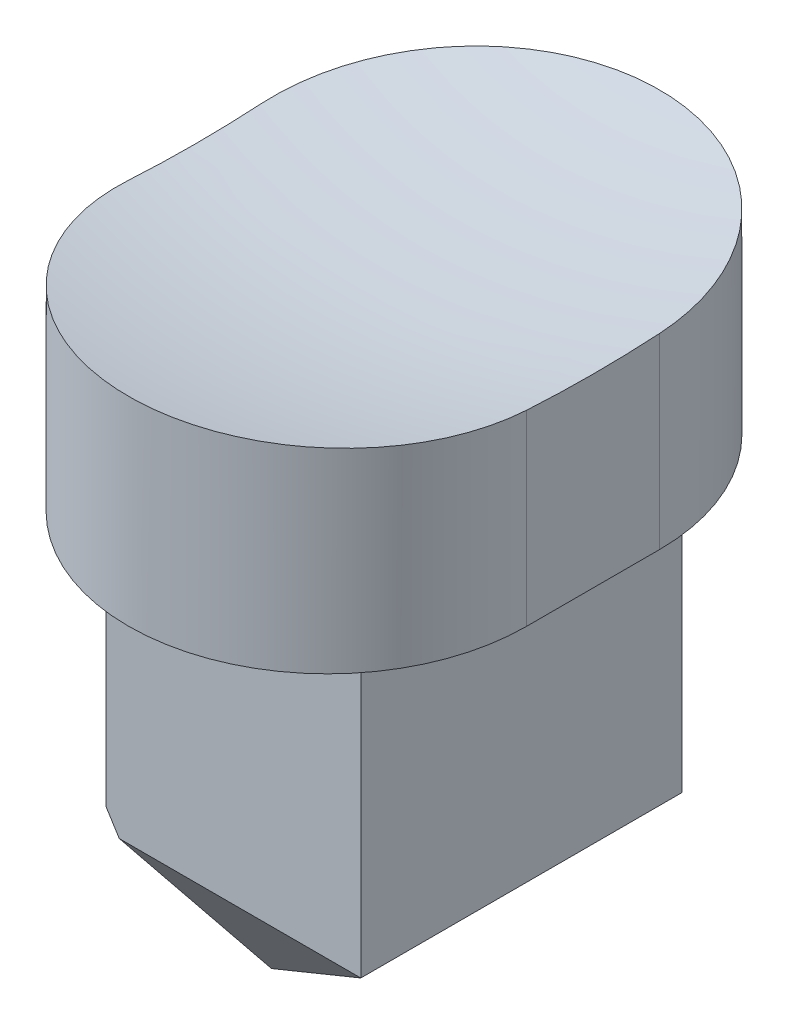
SolidWorks part; units mm, degrees
ref_plane "Front Plane" through (0, 0, 0) normal (0, 0, 1) x (1, 0, 0)
ref_plane "Top Plane" through (0, 0, 0) normal (0, 1, 0) x (1, 0, 0)
ref_plane "Right Plane" through (0, 0, 0) normal (1, 0, 0) x (0, 0, -1)
sketch "Sketch1" plane through (0, 0, 0) normal (0, 1, 0) x (1, 0, 0)
  line L1 (-9.6, 12.1) -> (9.6, 12.1)
  line L2 (-9.6, 12.1) -> (-9.6, -12.1)
  line L3 (-9.6, -12.1) -> (9.6, -12.1)
  line L4 (9.6, 12.1) -> (9.6, -12.1)
  line L5 (-9.6, 12.1) -> (9.6, -12.1) construction
  line L6 (-9.6, -12.1) -> (9.6, 12.1) construction
  point P0 (0, 0)
  dimension "D1" = 19.2
  dimension "D2" = 24.2
extrude "Boss-Extrude1" add sketch "Sketch1" along normal blind 22.1
sketch "Sketch2" plane through (0, 22.1, 0) normal (0, 1, 0) x (1, 0, 0)
  line L0 (0, 5) -> (0, -5) construction
  line L1 (15, 5) -> (15, -5)
  line L2 (-15, 5) -> (-15, -5)
  line L3 (0, 20) -> (0, -20) construction
  line L4 (-9.6, 0) -> (9.6, 0) construction
  line L5 (-9.6, 12.1) -> (-9.6, -12.1) construction
  line L6 (9.6, -12.1) -> (9.6, 12.1) construction
  arc A0 (15, 5) -> (-15, 5) centre (0, 5) ccw
  arc A1 (-15, -5) -> (15, -5) centre (0, -5) ccw
  point P3 (0, 0)
  dimension "D1" = 30
  dimension "D2" = 40
extrude "Boss-Extrude2" add sketch "Sketch2" along normal blind 15
sketch "Sketch4" plane through (-9.6, 0, 0) normal (-1, 0, 0) x (0, 0, 1)
  line L0 (0, 0) -> (0, -15) construction
  line L1 (-12.1, 0) -> (0, -15)
  line L2 (0, -15) -> (12.1, 0)
  line L3 (12.1, 0) -> (-12.1, 0)
  dimension "D1" = 15
extrude "Boss-Extrude3" add sketch "Sketch4" against normal blind 5
sketch "Sketch6" plane through (0, 0, 0) normal (0, 0, 1) x (1, 0, 0)
  line L0 (-4.6, -5) -> (9.6, 0)
  line L1 (-4.6, -15) -> (-4.6, 0) construction
  line L3 (-4.6, -5) -> (-4.6, 0)
  line L4 (-4.6, 0) -> (9.6, 0)
  dimension "D1" = 10
extrude "Boss-Extrude4" add sketch "Sketch6" along normal mid plane 3
fillet "Fillet1" radius 3 2 edges at (-4.6, 0, -6.8) (-4.6, 0, 6.8)
sketch "Sketch8" plane through (0, 0, 0) normal (1, 0, 0) x (0, 0, -1)
  line L0 (-85.2784, 120) -> (85.2784, 120) construction
  line L1 (-85.2784, 120) -> (85.2784, 120)
  line L2 (0, 120) -> (0, 34.7216) construction
  arc A0 (-85.2784, 120) -> (85.2784, 120) centre (0, 120) ccw
  dimension "D1" = 120
revolve "Cut-Revolve3" cut sketch "Sketch8" angle 360 about L1
sketch "Sketch9" plane through (0, 22.1, 0) normal (0, -1, 0) x (1, 0, 0)
  line L4 (9.6, -12.1) -> (-9.6, -12.1) construction
  line L5 (-9.6, -12.1) -> (-9.6, 12.1) construction
  line L6 (-9.6, 12.1) -> (9.6, 12.1) construction
  line L7 (9.6, 12.1) -> (9.6, -12.1) construction
  line L8 (9.6, -12.1) -> (-9.6, -12.1)
  line L9 (-9.6, -12.1) -> (-9.6, 12.1)
  line L10 (-9.6, 12.1) -> (9.6, 12.1)
  line L11 (9.6, 12.1) -> (9.6, -12.1)
extrude "Cut-Extrude-Thin1" cut sketch "Sketch9" against normal blind 10 thin thin type one direction wall 0.3
sketch "Sketch10" plane through (-9.6, 0, 0) normal (-1, 0, 0) x (0, 0, 1)
  line L0 (-12.4, 32.1) -> (12.4, 32.1) construction
  line L1 (-12.4, 32.1) -> (12.4, 32.1)
  line L2 (-12.4, 32.1) -> (-12.4, 32.4)
  line L3 (-12.4, 32.4) -> (12.4, 32.4)
  line L4 (12.4, 32.1) -> (12.4, 32.4)
  line L5 (-12.4, 32.1) -> (-12.4, 22.1) construction
  point P8 (12.4, 32.1)
  dimension "D1" = 0.3
extrude "Cut-Extrude1" cut sketch "Sketch10" against normal up to surface (19.2 mm away) up to face at (9.6, 10.7, 0)
sketch "Sketch12" plane through (0, 32.1, 0) normal (0, -1, 0) x (1, 0, 0)
  line L1 (-9.9, 12.4) -> (9.9, 12.4)
  line L2 (-9.9, 12.4) -> (-9.9, -12.4)
  line L3 (-9.9, -12.4) -> (9.9, -12.4)
  line L4 (9.9, 12.4) -> (9.9, -12.4)
extrude "Cut-Extrude3" cut sketch "Sketch12" against normal up to surface (0.3 mm away) up to face at (0, 32.4, 0)
sketch "Sketch13" plane through (9.6, 0, 0) normal (1, 0, 0) x (0, 0, -1)
  line L0 (12.1, 32.1) -> (12.1, 0) construction
  line L1 (-12.1, 0) -> (12.1, 0)
  line L2 (-12.1, 0) -> (-12.1, -15)
  line L3 (-12.1, -15) -> (12.1, -15)
  line L4 (12.1, 0) -> (12.1, -15)
  point P5 (11.1665, -16.55)
extrude "Cut-Extrude4" cut sketch "Sketch13" against normal through all
ref_plane "15 mm" through (0, -15, 0) normal (0, -1, 0) x (-1, 0, 0)
chamfer "Chamfer1" distance 0.75 angle 45 4 edges at (9.9, 22.1, 0) (0, 22.1, -12.4) (-9.9, 22.1, 0) (0, 22.1, 12.4)
chamfer "Chamfer2" distance 0.75 angle 45 4 edges at (0, 32.1, -12.1) (9.6, 32.1, 0) (0, 32.1, 12.1) (-9.6, 32.1, 0)
sketch "Sketch19" plane through (0, 0, -12.1) normal (0, 0, -1) x (-1, 0, 0)
  line L0 (-9.6, 0) -> (9.6, 0)
  line L1 (9.6, 0) -> (9.6, -15)
  line L2 (9.6, -15) -> (-9.6, 0)
  dimension "D1" = 15
extrude "Boss-Extrude5" add sketch "Sketch19" against normal up to surface (24.2 mm away) up to face at (0, 15.675, 12.1)
sketch "Sketch20" plane through (9.6, 0, 0) normal (1, 0, 0) x (0, 0, -1)
  line L0 (-12.1, 0) -> (0, -15)
  line L1 (-12.1, -15) -> (12.1, -15) construction
  line L2 (0, -15) -> (12.1, 0)
  line L4 (-12.1, 0) -> (-12.1, -15)
  line L5 (-12.1, -15) -> (12.1, -15)
  line L6 (12.1, -15) -> (12.1, 0)
extrude "Cut-Extrude5" cut sketch "Sketch20" against normal up to surface (19.2 mm away) contours L4 L5 L0 | L5 L6 L2 region at (9.6, -10, -8.0667) region at (9.6, -10, 8.0667) up to face at (-9.6, 8.175, 0)
chamfer "Chamfer3" distance 1 angle 45 2 edges at (-9.6, -7.5, 6.05) (-9.6, -7.5, -6.05)
equation "\"Hole Length\"= 25"
equation "\"Hole Height\"= 20"
equation "\"Shell Thickness\"= 5"
equation "\"Can Diameter\"= 66.3"
equation "\"Hole Tolerance\"= 0.8"
equation "\"D1@Sketch1\"=\"Hole Height\"-\"Hole Tolerance\""
equation "\"D2@Sketch1\"=\"Hole Length\"-\"Hole Tolerance\""
equation "\"D1@Sketch2\"=\"Hole Height\"+10"
equation "\"D2@Sketch2\"=\"Hole Length\"+15"
equation "\"D1@Boss-Extrude1\"=\"Shell Thickness\"+17.1"
equation "\"Blade thickness\"= 5"
equation "\"D1@Boss-Extrude3\"=\"Blade thickness\""
